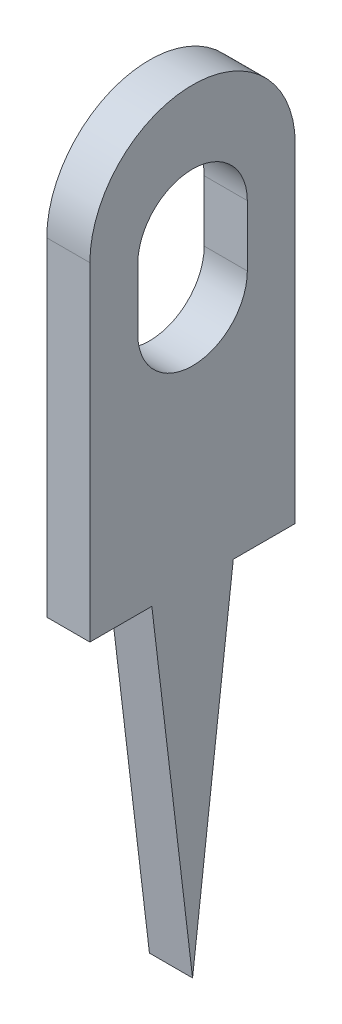
SolidWorks part; units mm, degrees
ref_plane "Front Plane" through (0, 0, 0) normal (0, 0, 1) x (1, 0, 0)
ref_plane "Top Plane" through (0, 0, 0) normal (0, 1, 0) x (1, 0, 0)
ref_plane "Right Plane" through (0, 0, 0) normal (1, 0, 0) x (0, 0, -1)
sketch "Sketch2" plane through (0, 0, 0) normal (1, 0, 0) x (0, 0, -1)
  line L0 (0, 0) -> (0, 6.3) construction
  line L1 (1.5, 0) -> (0.595, 0)
  line L2 (0, 0) -> (0, -5) construction
  line L3 (1.5, 0) -> (1.5, 4.8)
  line L4 (-0.6621, 3.99) -> (0.6621, 3.99) construction
  line L5 (0.595, 0) -> (0, -5)
  line L6 (0, 3.545) -> (0, 4.435) construction
  line L7 (-0.8, 3.545) -> (-0.8, 4.435)
  line L8 (0.8, 3.545) -> (0.8, 4.435)
  line L9 (-0.595, 0) -> (0, -5)
  line L10 (-1.5, 0) -> (-0.595, 0)
  line L11 (-1.5, 0) -> (-1.5, 4.8)
  arc A0 (1.5, 4.8) -> (-1.5, 4.8) centre (0, 4.8) ccw
  arc A1 (-0.8, 3.545) -> (0.8, 3.545) centre (0, 3.545) ccw
  arc A2 (0.8, 4.435) -> (-0.8, 4.435) centre (0, 4.435) ccw
  point P4 (0, 0)
  point P12 (0, 3.99)
  point P14 (0, 3.99)
  point P19 (0, 5.235)
  point P20 (0, 2.745)
  point P24 (0, 6.3)
  point P25 (0, 0)
  dimension "D1" = 1.5
  dimension "D2" = 5
  dimension "D3" = 6.3
  dimension "D4" = 3.99
  dimension "D5" = 0.595
  dimension "D6" = 1.6
  dimension "D7" = 2.49
extrude "Boss-Extrude1" add sketch "Sketch2" along normal blind 0.315 and the other way blind 0.315
